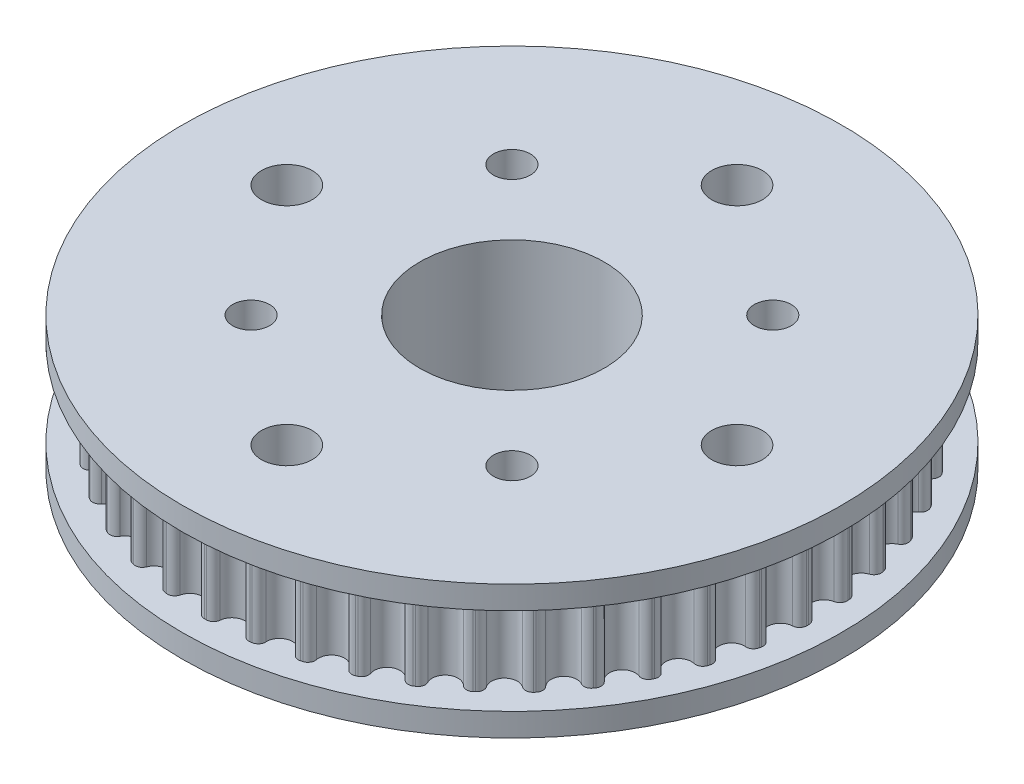
SolidWorks part; units mm, degrees
ref_plane "Front Plane" through (0, 0, 0) normal (0, 0, 1) x (1, 0, 0)
ref_plane "Top Plane" through (0, 0, 0) normal (0, 1, 0) x (1, 0, 0)
ref_plane "Right Plane" through (0, 0, 0) normal (1, 0, 0) x (0, 0, -1)
sketch "Sketch1" plane through (0, 0, 0) normal (0, 1, 0) x (1, 0, 0)
  line L0 (0, 0) -> (0, 21.1048) construction
  line L1 (0, 0) -> (2.8913, 20.5726) construction
  circle A0 centre (0, 0) radius 21.1048 construction
  circle A1 centre (0, 0) radius 19.8848 construction
  circle A2 centre (0, 20.7748) radius 0.89 construction
  circle A5 centre (2.8913, 20.5726) radius 0.89 construction
  arc A6 (0, 19.8848) -> (0.8792, 20.6366) centre (0, 20.7748) ccw
  arc A7 (0.8792, 20.6366) -> (1.4065, 21.0579) centre (1.3731, 20.559) cw
  arc A8 (1.5379, 21.0487) -> (2.0014, 20.5582) centre (1.5015, 20.55) cw
  arc A9 (2.7674, 19.6913) -> (2.0014, 20.5582) centre (2.8913, 20.5726) cw
  arc A10 (1.4065, 21.0579) -> (1.5379, 21.0487) centre (0, 0) cw
  arc A11 (0, 19.8848) -> (2.7674, 19.6913) centre (0, 0) ccw
  dimension "D1" = 42.2096
  dimension "D3" = 1.78
  dimension "D4" = 0.5
  dimension "D2" = 1.22
  dimension "D5" = 8
extrude "Boss-Extrude1" add sketch "Sketch1" along normal mid plane 6
ref_axis "Axis1" through (0, 3.3, 0) along (0, -1, 0)
pattern_circular "CirPattern1" count 45 over 360 about axis through (0, 3.3, 0) along (0, -1, 0) of "Boss-Extrude1"
sketch "Sketch2" plane through (0, 0, 0) normal (1, 0, 0) x (0, 0, -1)
  line L0 (-20.6477, 3) -> (-21.1047, 3) construction
  line L4 (22.6922, 4.5875) -> (6.35, 4.5875)
  line L5 (22.6922, 4.5875) -> (22.6922, 3)
  line L6 (-22.6922, 3) -> (22.6922, 3) construction
  line L7 (-22.6922, 3) -> (-22.6922, 4.5875) construction
  line L8 (-22.6922, 4.5875) -> (22.6922, 4.5875) construction
  line L9 (22.6922, 3) -> (22.6922, 4.5875) construction
  line L10 (-22.6922, 3) -> (22.6922, 4.5875) construction
  line L11 (-22.6922, 4.5875) -> (22.6922, 3) construction
  line L12 (-21.1047, 3) -> (-21.1047, -3) construction
  line L13 (0, 3.3) -> (0, -3.3) construction
  line L14 (6.35, 4.5875) -> (6.35, 3)
  line L16 (22.6922, 3) -> (6.35, 3)
  line L17 (6.35, 4.5875) -> (6.35, 3)
  point P0 (0, 3.7937)
  dimension "D1" = 1.5875
  dimension "D2" = 1.5875
  dimension "D3" = 6.35
revolve "Revolve3" add sketch "Sketch2" angle 360 about axis through (0, 3.3, 0) along (0, -1, 0) region at (0, 3.7937, -14.5211)
mirror "Mirror1" about plane through (0, 0, 0) normal (0, 1, 0) of "Revolve3"
sketch "Sketch3" plane through (0, 3, 0) normal (0, 1, 0) x (1, 0, 0)
  line L1 (-8.9803, -8.9803) -> (8.9803, -8.9803) construction
  line L2 (-8.9803, -8.9803) -> (-8.9803, 8.9803) construction
  line L3 (-8.9803, 8.9803) -> (8.9803, 8.9803) construction
  line L4 (8.9803, -8.9803) -> (8.9803, 8.9803) construction
  line L5 (-8.9803, -8.9803) -> (8.9803, 8.9803) construction
  line L6 (-8.9803, 8.9803) -> (8.9803, -8.9803) construction
  circle A0 centre (-15.5, 0) radius 1.7462
  circle A1 centre (0, 0) radius 6.35
  circle A2 centre (0, 0) radius 6.35
  circle A3 centre (0, 15.5) radius 1.7462
  circle A4 centre (15.5, 0) radius 1.7462
  circle A5 centre (0, -15.5) radius 1.7462
  circle A6 centre (-8.9803, 8.9803) radius 1.27
  circle A7 centre (8.9803, 8.9803) radius 1.27
  circle A8 centre (8.9803, -8.9803) radius 1.27
  circle A9 centre (-8.9803, -8.9803) radius 1.27
  point P7 (8.1469, 8.1469)
  point P14 (0, 0)
  dimension "D3" = 3.4925
  dimension "D5" = 2.54
  dimension "D2" = 15.5
  dimension "D6" = 25.4
  dimension "D1" = 0
  dimension "D4" = 4
extrude "Cut-Extrude1" cut sketch "Sketch3" against normal through all both and the other way through all
equation "\"TEETH_NUM\" = 45"
equation "\"TOOTH_PITCH\"= 3mm"
equation "\"PITCH_LINE_OFFSET\"= .015in"
equation "\"DIAMETER_PER_GROOVE\"= .954925mm"
equation "\"PITCH_DIAMETER\"= \"TEETH_NUM\" * \"DIAMETER_PER_GROOVE\""
equation "\"OUTSIDE_DIAMETER\"= \"PITCH_DIAMETER\" - \"PITCH_LINE_OFFSET\" * 2"
equation "\"D1@Sketch1\"=\"OUTSIDE_DIAMETER\""
equation "\"TOOTH_HEIGHT\"= 1.22mm"
equation "\"D2@Sketch1\"=\"TOOTH_HEIGHT\""
equation "\"TOOTH_DIAMETER\"= 1.78mm"
equation "\"INTERNAL_RADIUS\"= .5mm"
equation "\"D3@Sketch1\"=\"TOOTH_DIAMETER\""
equation "\"D5@Sketch1\"=360 / \"TEETH_NUM\""
equation "\"D4@Sketch1\"=\"INTERNAL_RADIUS\""
equation "\"D1@CirPattern1\"=\"TEETH_NUM\""
